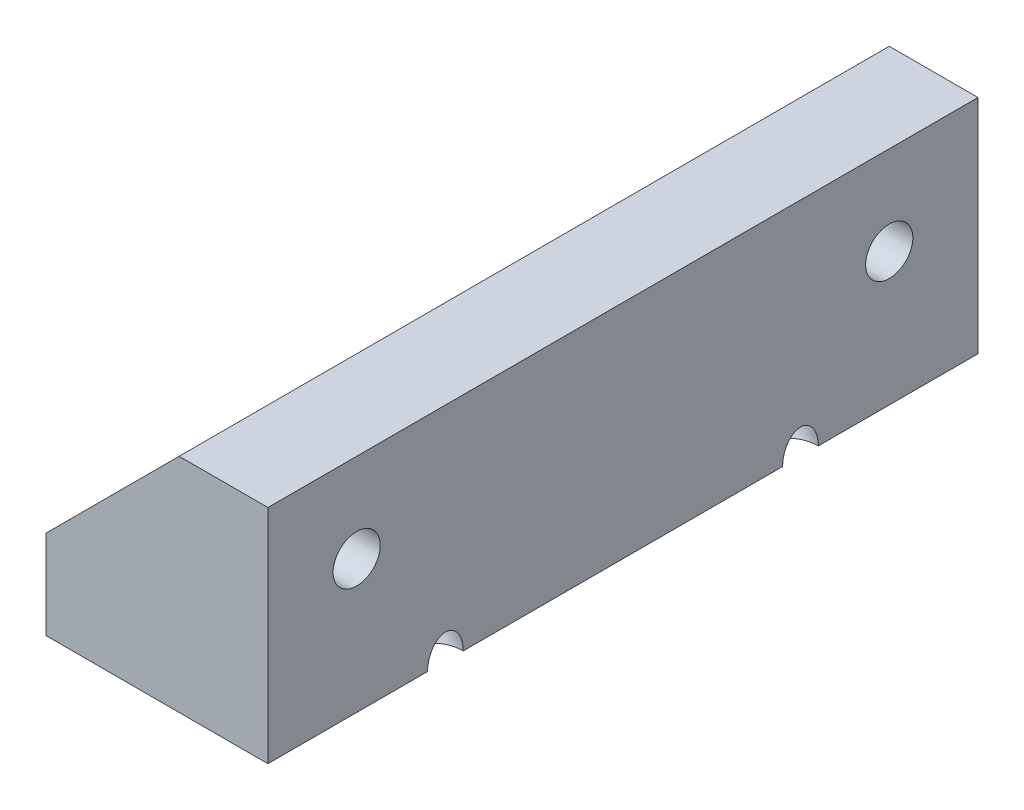
SolidWorks part; units mm, degrees
ref_plane "Front" through (0, 0, 0) normal (0, 0, 1) x (1, 0, 0)
ref_plane "Top" through (0, 0, 0) normal (0, 1, 0) x (1, 0, 0)
ref_plane "Right" through (0, 0, 0) normal (1, 0, 0) x (0, 0, -1)
sketch "Sketch1" plane through (0, 0, 0) normal (0, 1, 0) x (1, 0, 0)
  line L1 (-15.875, -50.8) -> (15.875, -50.8)
  line L2 (-15.875, -50.8) -> (-15.875, 50.8)
  line L3 (-15.875, 50.8) -> (15.875, 50.8)
  line L4 (15.875, -50.8) -> (15.875, 50.8)
  line L5 (-15.875, -50.8) -> (15.875, 50.8) construction
  line L6 (-15.875, 50.8) -> (15.875, -50.8) construction
  point P0 (0, 0)
  dimension "D1" = 101.6
  dimension "D2" = 31.75
extrude "Boss-Extrude1" add sketch "Sketch1" along normal mid plane 31.75 contours L3 L4 L1 L2
sketch "Sketch2" plane through (0, 0, 50.8) normal (0, 0, 1) x (1, 0, 0)
  line L0 (-15.875, -3.175) -> (-15.875, 15.875)
  line L1 (-15.875, 15.875) -> (-15.875, -15.875) construction
  line L2 (-15.875, 15.875) -> (3.175, 15.875)
  line L3 (-15.875, 15.875) -> (15.875, 15.875) construction
  line L4 (3.175, 15.875) -> (-15.875, -3.175)
  line L5 (15.875, 15.875) -> (15.875, -15.875) construction
  dimension "D1" = 45
  dimension "D2" = 12.7
extrude "Cut-Extrude1" cut sketch "Sketch2" against normal up to next
sketch "Sketch3" plane through (-6.35, 6.35, 0) normal (-0.7071, 0.7071, 0) x (0, 0, 1)
  line L0 (-25.4, 0) -> (25.4, 0) construction
  line L1 (50.8, -13.4704) -> (50.8, 13.4704) construction
  line L2 (0, -50) -> (0, 50) construction
  point P0 (-25.4, 0)
  point P1 (25.4, 0)
  point P6 (50.8, 0)
  point P7 (0, 0)
  dimension "D1" = 50.8
hole_wizard "1/4-20 Tapped Hole1" positions "Sketch4" profile "Sketch6" tap size "1/4-20" standard "ANSI Inch" end condition up to next
sketch "Sketch4" plane through (-6.35, 6.35, 0) normal (-0.7071, 0.7071, 0) x (0, 0, 1)
  point P0 (-25.4, 0)
  point P3 (25.4, 0)
cosmetic thread "Hole Thread1" parameters "D2"=6.35
cosmetic thread "Hole Thread2" parameters "D2"=6.35
sketch "Sketch6" plane through (-6.35, 6.35, -25.4) normal (0, 0, 1) x (-0.7071, -0.7071, 0)
  line L0 (0, 0) -> (0, 31.4309)
  line L1 (0, 31.4309) -> (2.5527, 31.4309)
  line L2 (2.5527, 31.4309) -> (2.5527, 0)
  line L5 (2.5527, 0) -> (0, 0)
  line L11 (0, -6.35) -> (0, 107.95) construction
  dimension "Thru Tap Drill Dia." = 5.1054
  dimension "Thru Tap Drill Depth" = 31.4309
ref_plane "Plane1" through (-15.875, 0, 0) normal (-1, 0, 0) x (0, 0, 1)
sketch "Sketch7" plane through (-15.875, 0, 0) normal (1, 0, 0) x (0, 0, -1)
  line L0 (-38.1, 3.175) -> (38.1, 3.175) construction
  line L1 (0, 50) -> (0, -50) construction
  line L2 (-50.8, 15.875) -> (-50.8, -15.875) construction
  line L3 (-50.8, 15.875) -> (50.8, 15.875) construction
  point P0 (-38.1, 3.175)
  point P1 (38.1, 3.175)
  point P2 (0, 3.175)
  dimension "D1" = 12.7
  dimension "D2" = 12.7
hole_wizard "CBORE for 1/4 Socket Head Cap Screw1" positions "Sketch14" profile "Sketch15" counterbore size "1/4" standard "ANSI Inch" end condition through all
sketch "Sketch14" plane through (-15.875, 0, 0) normal (-1, 0, 0) x (0, 0, 1)
  point P0 (-38.1, 3.175)
  point P3 (38.1, 3.175)
sketch "Sketch15" plane through (-15.875, 3.175, -38.1) normal (0, 1, 0) x (0, 0, 1)
  line L0 (0, 0) -> (0, 31.75)
  line L1 (0, 31.75) -> (3.3782, 31.75)
  line L3 (3.3782, 31.75) -> (3.3782, 20.32)
  line L4 (3.3782, 20.32) -> (5.5562, 20.32)
  line L5 (5.5562, 20.32) -> (5.5562, 0)
  line L7 (5.5562, 0) -> (0, 0)
  line L11 (0, -6.35) -> (0, 107.95) construction
  dimension "Thru Hole Dia." = 6.7564
  dimension "Thru Hole Depth" = 31.75
  dimension "C'Bore Dia." = 11.1125
  dimension "C'Bore Depth" = 20.32
ref_plane "Plane2" through (-6.35, 6.35, 0) normal (-0.7071, 0.7071, 0) x (0, 0, 1)
ref_plane "Plane3" through (0, -15.875, 0) normal (0, -1, 0) x (-1, 0, 0)
ref_axis "Axis1" through (-15.875, -15.875, 55.88) along (0, 0, -1)
ref_plane "Plane4" through (-15.875, -15.875, 0) normal (0.7071, 0.7071, 0) x (0, 0, -1)
ref_axis "Axis2" through (-22.225, -9.525, -98.0543) along (0, 0, 1)
ref_axis "Axis3" through (-15.875, -3.175, 55.88) along (0, 0, -1)
